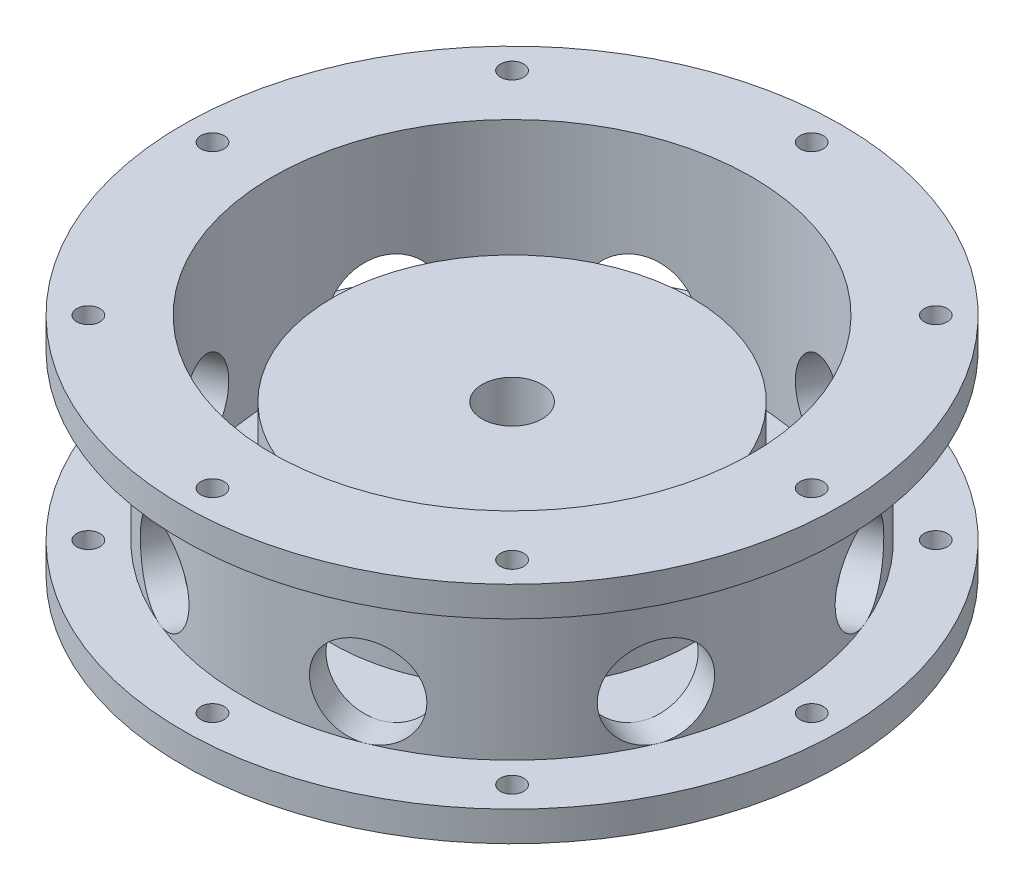
SolidWorks part; units mm, degrees
material "AISI 316 Annealed Stainless Steel Bar (SS)"
ref_plane "Front Plane" through (0, 0, 0) normal (0, 0, 1) x (1, 0, 0)
ref_plane "Top Plane" through (0, 0, 0) normal (0, 1, 0) x (1, 0, 0)
ref_plane "Right Plane" through (0, 0, 0) normal (1, 0, 0) x (0, 0, -1)
sketch "Sketch1" plane through (0, 0, 0) normal (0, 0, 1) x (1, 0, 0)
  line L0 (0, 0) -> (0, 20.1477) construction
  line L1 (69.85, 0) -> (6.35, 0)
  line L2 (69.85, 0) -> (69.85, 6.35)
  line L3 (69.85, 6.35) -> (57.15, 6.35)
  line L4 (57.15, 6.35) -> (57.15, 41.275)
  line L5 (57.15, 41.275) -> (69.85, 41.275)
  line L6 (69.85, 41.275) -> (69.85, 47.625)
  line L7 (69.85, 47.625) -> (50.8, 47.625)
  line L8 (50.8, 47.625) -> (50.8, 6.35)
  line L9 (50.8, 6.35) -> (38.1, 6.35)
  line L10 (38.1, 6.35) -> (38.1, 31.75)
  line L11 (38.1, 31.75) -> (6.35, 31.75)
  line L12 (6.35, 31.75) -> (6.35, 0)
  point P3 (0, 0)
  dimension "D1" = 6.35
  dimension "D2" = 50.8
  dimension "D3" = 6.35
  dimension "D4" = 12.7
  dimension "D5" = 15.875
  dimension "D6" = 6.35
  dimension "D7" = 25.4
  dimension "D8" = 6.35
  dimension "D9" = 12.7
revolve "Revolve1" add sketch "Sketch1" angle 360 about L0
hole_wizard "#10 (0.1935) Diameter Hole2" positions "Sketch3" profile "Sketch4" hole size "#10" standard "ANSI Inch" end condition through all
sketch "Sketch3" plane through (0, 47.625, 0) normal (0, 1, 0) x (1, 0, 0)
  line L0 (0, 63.5) -> (0, 69.85) construction
  line L1 (0, 69.85) -> (-28.4116, 69.85) construction
  circle A0 centre (0, 0) radius 69.85 construction
  point P0 (0, 63.5)
  point P11 (0, 0)
  dimension "D1" = 6.35
sketch "Sketch4" plane through (0, 47.625, -63.5) normal (1, 0, 0) x (0, 0, 1)
  line L0 (0, 0) -> (0, 47.625)
  line L1 (0, 47.625) -> (2.4574, 47.625)
  line L2 (2.4574, 47.625) -> (2.4574, 0)
  line L5 (2.4574, 0) -> (0, 0)
  line L11 (0, -6.35) -> (0, 107.95) construction
  dimension "Thru Hole Dia." = 4.9149
  dimension "Thru Hole Depth" = 47.625
pattern_circular "CirPattern1" count 8 over 360 about axis through (0, 0, 0) along (0, -1, 0) of "#10 (0.1935) Diameter Hole2" reverse direction yes
ref_plane "Plane1" through (21.8704, 0, -52.7997) normal (0.3827, 0, -0.9239) x (0, -1, 0)
sketch "Sketch5" plane through (21.8704, 0, -52.7997) normal (0.3827, 0, -0.9239) x (0, -1, 0)
  line L0 (-6.35, 57.15) -> (-6.35, -57.15) construction
  line L1 (-15.875, 0) -> (-6.35, 0) construction
  circle A0 centre (-15.875, 0) radius 9.525
  point P4 (0, 0)
  dimension "D1" = 19.05
extrude "Cut-Extrude1" cut sketch "Sketch5" against normal up to next
pattern_circular "CirPattern2" count 8 over 360 about axis through (0, 0, 0) along (0, -1, 0) of "Cut-Extrude1" reverse direction yes
